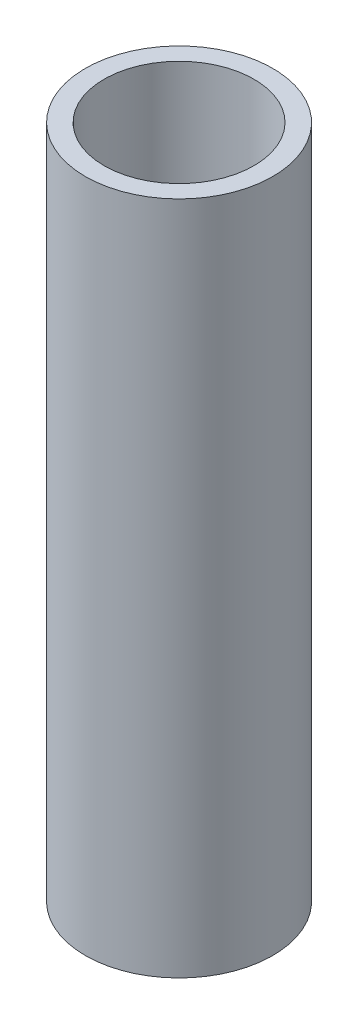
SolidWorks part; units mm, degrees
ref_plane "Front" through (0, 0, 0) normal (0, 0, 1) x (1, 0, 0)
ref_plane "Top" through (0, 0, 0) normal (0, 1, 0) x (1, 0, 0)
ref_plane "Right" through (0, 0, 0) normal (1, 0, 0) x (0, 0, -1)
sketch "Sketch1" plane through (0, 0, 0) normal (0, 1, 0) x (1, 0, 0)
  circle A0 centre (0, 0) radius 15.875
  circle A1 centre (0, 0) radius 12.7
  dimension "D1" = 31.75
  dimension "D2" = 25.4
extrude "Boss-Extrude1" add sketch "Sketch1" along normal mid plane 114.3
